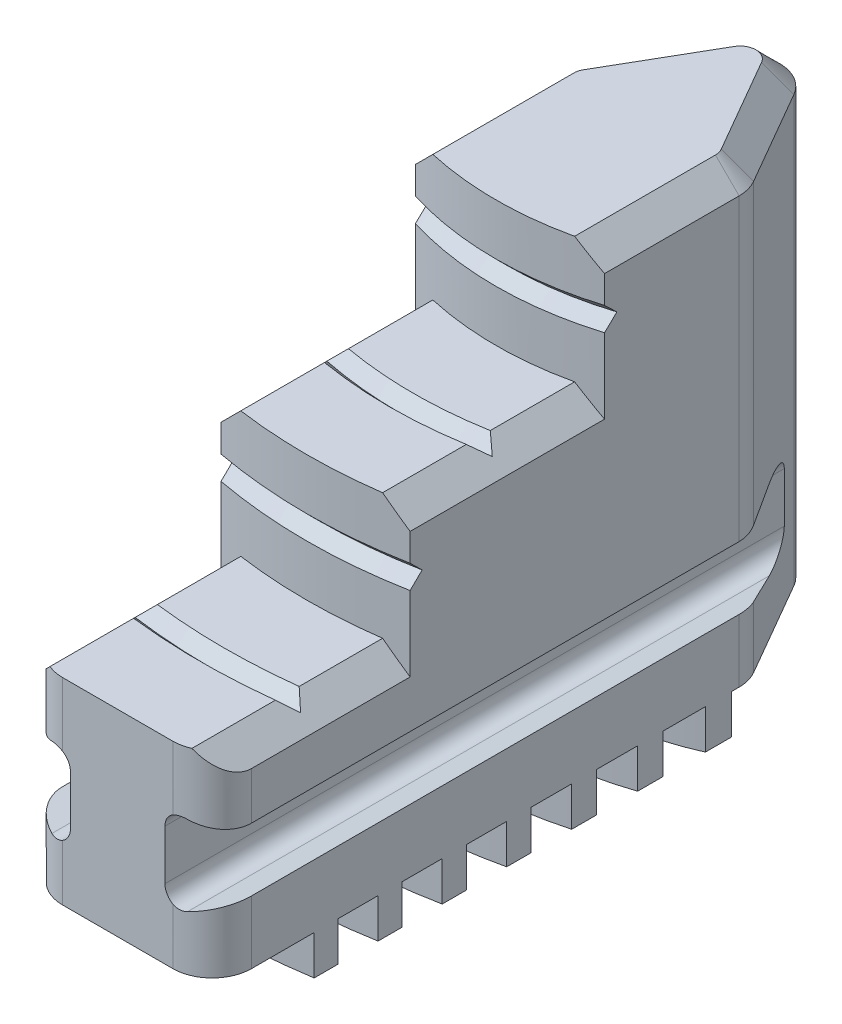
SolidWorks part; units mm, degrees
material "Alloy Steel"
ref_plane "Front Plane" through (0, 0, 0) normal (0, 0, 1) x (1, 0, 0)
ref_plane "Top Plane" through (0, 0, 0) normal (0, 1, 0) x (1, 0, 0)
ref_plane "Right Plane" through (0, 0, 0) normal (1, 0, 0) x (0, 0, -1)
sketch "Sketch1" plane through (0, 0, 0) normal (0, 1, 0) x (1, 0, 0)
  line L1 (12, 5) -> (12, 66.8756)
  line L2 (11.3301, 69.3756) -> (4.3301, 81.5)
  line L3 (0, 84) -> (0, 0) construction
  line L4 (7, 0) -> (-7, 0)
  line L5 (-11.3301, 69.3756) -> (-4.3301, 81.5)
  line L6 (-12, 5) -> (-12, 66.8756)
  line L7 (0, 84) -> (0, 89) construction
  line L8 (0, 89) -> (4.3301, 81.5) construction
  arc A0 (12, 66.8756) -> (11.3301, 69.3756) centre (7, 66.8756) ccw
  arc A1 (4.3301, 81.5) -> (-4.3301, 81.5) centre (0, 79) ccw
  arc A2 (12, 5) -> (7, 0) centre (7, 5) cw
  arc A3 (-12, 5) -> (-7, 0) centre (-7, 5) ccw
  arc A4 (-12, 66.8756) -> (-11.3301, 69.3756) centre (-7, 66.8756) cw
  dimension "D2" = 5
  dimension "D1" = 84
  dimension "D3" = 24
  dimension "D4" = 30
extrude "Boss-Extrude1" add sketch "Sketch1" along normal blind 62
sketch "Sketch2" plane through (0, 0, 0) normal (1, 0, 0) x (0, 0, -1)
  line L0 (48, 62) -> (48, 55.5)
  line L1 (5, 62) -> (66.8756, 62) construction
  line L2 (48, 55.5) -> (49.5, 54)
  line L3 (49.5, 54) -> (48, 52.5)
  line L4 (48, 52.5) -> (48, 46)
  line L5 (48, 46) -> (24, 46) construction
  line L6 (24, 46) -> (24, 39.5)
  line L7 (24, 39.5) -> (25.5, 38)
  line L8 (25.5, 38) -> (24, 36.5)
  line L9 (24, 36.5) -> (24, 30)
  line L10 (24, 30) -> (0, 30) construction
  line L16 (0, 62) -> (0, 0) construction
  line L17 (-12, 30) -> (-12, 62)
  line L18 (-12, 62) -> (48, 62)
  line L19 (15, 5) -> (20, 5)
  line L20 (20, 5) -> (20, 0)
  line L21 (5, 0) -> (66.8756, 0) construction
  line L22 (20, 0) -> (15, 0)
  line L23 (15, 0) -> (15, 5)
  line L24 (23, 0) -> (23, 5)
  line L25 (23, 5) -> (28, 5)
  line L26 (28, 5) -> (28, 0)
  line L27 (28, 0) -> (23, 0)
  line L28 (31, 0) -> (31, 5)
  line L29 (31, 5) -> (36, 5)
  line L30 (36, 5) -> (36, 0)
  line L31 (36, 0) -> (31, 0)
  line L32 (39, 0) -> (39, 5)
  line L33 (39, 5) -> (44, 5)
  line L34 (44, 5) -> (44, 0)
  line L35 (44, 0) -> (39, 0)
  line L36 (47, 0) -> (47, 5)
  line L37 (47, 5) -> (52, 5)
  line L38 (52, 5) -> (52, 0)
  line L39 (52, 0) -> (47, 0)
  line L40 (55, 0) -> (55, 5)
  line L41 (55, 5) -> (60, 5)
  line L42 (60, 5) -> (60, 0)
  line L43 (60, 0) -> (55, 0)
  line L52 (84, 3) -> (84, 59) construction
  line L53 (63, 0) -> (84, 0)
  line L54 (63, 0) -> (63, 5)
  line L55 (63, 5) -> (84, 5)
  line L56 (84, 0) -> (84, 5)
  line L57 (89, 62) -> (89, 0) construction
  line L59 (49, 62) -> (48, 62) construction
  line L63 (84, 0) -> (89, 0) construction
  line L64 (5, 0) -> (66.8756, 0) construction
  line L65 (12, 0) -> (-12, 0)
  line L66 (12, 0) -> (12, 5)
  line L67 (12, 5) -> (-12, 5)
  line L68 (-12, 0) -> (-12, 5)
  line L69 (12, 0) -> (15, 0) construction
  line L70 (60, 0) -> (63, 0) construction
  line L71 (20, 0) -> (23, 0) construction
  line L72 (0, 30) -> (-12, 30)
  line L73 (10.5, 30) -> (12, 28.5)
  line L74 (12, 28.5) -> (13.5, 30)
  line L75 (13.5, 30) -> (24, 30)
  line L76 (10.5, 30) -> (0, 30)
  line L77 (24, 46) -> (34.5, 46)
  line L78 (34.5, 46) -> (36, 44.5)
  line L79 (36, 44.5) -> (37.5, 46)
  line L80 (37.5, 46) -> (48, 46)
  point P30 (36, 46)
  point P69 (12, 30)
  dimension "D1" = 135
  dimension "D2" = 1.5
  dimension "D3" = 16
  dimension "D4" = 24
  dimension "D5" = 5
  dimension "D6" = 5
  dimension "D8" = 3
  dimension "D9" = 12
  dimension "D10" = 12
  dimension "D7" = 6
revolve "Cut-Revolve2" cut sketch "Sketch2" angle 360 about L57 region at (0, 47.9636, -13.5976) region at (0, 2.5, -17.5) region at (0, 2.5, -25.5) region at (0, 2.5, -33.5) region at (0, 2.5, -41.5) region at (0, 2.5, -49.5) region at (0, 2.5, -57.5) region at (0, 2.5, -73.5) region at (0, 2.5, 0)
sketch "Sketch3" plane through (0, 0, 0) normal (0, 0, 1) x (1, 0, 0)
  line L0 (-12, 21) -> (-8.6014, 22.0716)
  line L1 (-12, 30) -> (-12, 5) construction
  line L2 (-6, 20.1641) -> (-6, 17)
  line L3 (-6, 17) -> (-12, 17) construction
  line L4 (-12, 17) -> (-12, 21)
  line L5 (-12, 17) -> (-12, 13)
  line L6 (-6, 13.8359) -> (-6, 17)
  line L7 (-12, 13) -> (-8.6014, 11.9284)
  line L8 (4.3301, 0) -> (-4.3301, 0) construction
  line L9 (0, 0) -> (0, 30) construction
  line L11 (12, 13) -> (8.6014, 11.9284)
  line L12 (12, 17) -> (12, 13)
  line L13 (12, 17) -> (12, 21)
  line L14 (12, 21) -> (8.6014, 22.0716)
  line L15 (6, 20.1641) -> (6, 17)
  line L16 (6, 13.8359) -> (6, 17)
  line L17 (-7, 30) -> (7, 30) construction
  arc A0 (-8.6014, 22.0716) -> (-6, 20.1641) centre (-8, 20.1641) cw
  arc A1 (-8.6014, 11.9284) -> (-6, 13.8359) centre (-8, 13.8359) ccw
  arc A2 (8.6014, 22.0716) -> (6, 20.1641) centre (8, 20.1641) ccw
  arc A3 (8.6014, 11.9284) -> (6, 13.8359) centre (8, 13.8359) cw
  dimension "D2" = 2
  dimension "D1" = 35
  dimension "D3" = 6
  dimension "D4" = 8
  dimension "D5" = 13
extrude "Cut-Extrude1" cut sketch "Sketch3" against normal through all both and the other way through all
chamfer "Chamfer2" distance 3 angle 45 11 edges at (12, 62, -58.3355) (11.8296, 62, -68.1697) (7.8301, 62, -75.4378) (0, 62, -84) (-7.8301, 62, -75.4378) (-11.8296, 62, -68.1697) (-12, 62, -58.3355) (-12, 46, -44.3565) (-12, 30, -19.7885) (12, 30, -19.7885) (12, 46, -44.3565)
